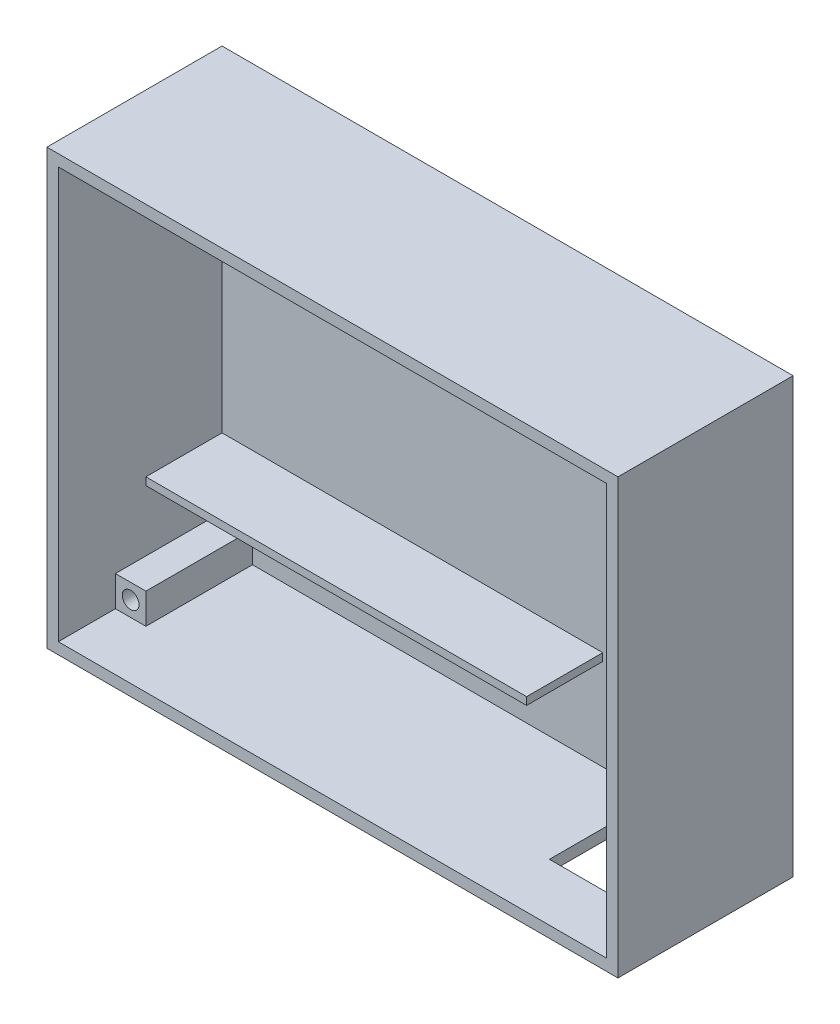
SolidWorks part; units mm, degrees
ref_plane "Front Plane" through (0, 0, 0) normal (0, 0, 1) x (1, 0, 0)
ref_plane "Top Plane" through (0, 0, 0) normal (0, 1, 0) x (1, 0, 0)
ref_plane "Right Plane" through (0, 0, 0) normal (1, 0, 0) x (0, 0, -1)
sketch "Sketch2" plane through (0, 0, 0) normal (0, 0, 1) x (1, 0, 0)
  line L1 (0, 0) -> (75, 0)
  line L2 (0, 0) -> (0, 57)
  line L3 (0, 57) -> (75, 57)
  line L4 (75, 0) -> (75, 57)
  dimension "D1" = 75
  dimension "D2" = 57
extrude "Body creation" add sketch "Sketch2" along normal blind 23
shell "Thikness of walls" thickness 1.5 removed face at (37.5, 28.5, 23)
ref_plane "Plane1" through (0, 28.5, 0) normal (0, -1, 0) x (-1, 0, 0)
sketch "Sketch6" plane through (0, 0, 1.5) normal (0, 0, 1) x (1, 0, 0)
  line L1 (1.5, 55.5) -> (5.5, 55.5)
  line L2 (1.5, 55.5) -> (1.5, 51.5)
  line L3 (1.5, 51.5) -> (5.5, 51.5)
  line L4 (5.5, 55.5) -> (5.5, 51.5)
  line L5 (73.5, 55.5) -> (69.5, 55.5)
  line L6 (73.5, 55.5) -> (73.5, 51.5)
  line L7 (73.5, 51.5) -> (69.5, 51.5)
  line L8 (69.5, 55.5) -> (69.5, 51.5)
  dimension "D1" = 4
extrude "Corner rect." add sketch "Sketch6" along normal blind 14
sketch "Sketch8" plane through (0, 0, 23) normal (0, 0, 1) x (1, 0, 0)
  line L0 (3.5, 53.5) -> (3.5, 51.5) construction
  line L1 (5.5, 51.5) -> (1.5, 51.5) construction
  line L2 (5.5, 53.5) -> (3.5, 53.5) construction
  line L3 (5.5, 55.5) -> (5.5, 51.5) construction
  line L4 (69.5, 53.5) -> (71.5, 53.5) construction
  line L5 (69.5, 55.5) -> (69.5, 51.5) construction
  line L7 (71.5, 53.5) -> (71.5, 51.5) construction
  line L8 (69.5, 51.5) -> (73.5, 51.5) construction
  circle A0 centre (3.5, 53.5) radius 1.1
  circle A1 centre (71.5, 53.5) radius 1.1
  dimension "D1" = 2.2
extrude "Screw hole" cut sketch "Sketch8" against normal up to surface (23 mm away) up to face at (37.5, 28.5, 0)
sketch "Sketch10" plane through (0, 0, 0) normal (0, 0, -1) x (-1, 0, 0)
  circle A0 centre (-71.5, 53.5) radius 1.75
  circle A1 centre (-3.5, 53.5) radius 1.75
  dimension "D1" = 3.5
extrude "Screw head" cut sketch "Sketch10" against normal blind 4
mirror "Mirror to other side" about plane through (0, 28.5, 0) normal (0, -1, 0) of "Screw head", "Corner rect.", "Screw hole"
sketch "Sketch5" plane through (0, 0, 0) normal (0, -1, 0) x (1, 0, 0)
  line L0 (0, 0) -> (75, 0) construction
  line L1 (67.5, 15.5) -> (58.5, 15.5)
  line L2 (67.5, 15.5) -> (67.5, 4.5)
  line L3 (67.5, 4.5) -> (58.5, 4.5)
  line L4 (58.5, 15.5) -> (58.5, 4.5)
  line L7 (63, 15.5) -> (63, 4.5) construction
  line L8 (75, 23) -> (75, 0) construction
  dimension "D1" = 11
  dimension "D2" = 9
  dimension "D3" = 15.5
  dimension "D4" = 12
extrude "Ports cut out" cut sketch "Sketch5" against normal up to surface (1.5 mm away) up to face at (37.5, 1.5, 13.875)
sketch "Sketch11" plane through (0, 0, 1.5) normal (0, 0, 1) x (1, 0, 0)
  line L0 (1.5, 51.5) -> (1.5, 5.5) construction
  line L1 (5.5, 51.5) -> (51.5, 51.5)
  line L3 (1.5, 14.5) -> (51.5, 14.5)
  line L5 (5.5, 52.5) -> (51.5, 52.5)
  line L6 (1.5, 13.5) -> (51.5, 13.5)
  line L7 (51.5, 14.5) -> (51.5, 13.5)
  line L8 (51.5, 52.5) -> (51.5, 51.5)
  line L9 (5.5, 52.5) -> (5.5, 51.5)
  line L10 (1.5, 14.5) -> (1.5, 13.5)
  point P6 (0, 0)
  point P11 (0, 0)
  dimension "D1" = 37
  dimension "D2" = 50
  dimension "D3" = 1
  dimension "D4" = 1
extrude "Battery Placement" add sketch "Sketch11" along normal blind 10
